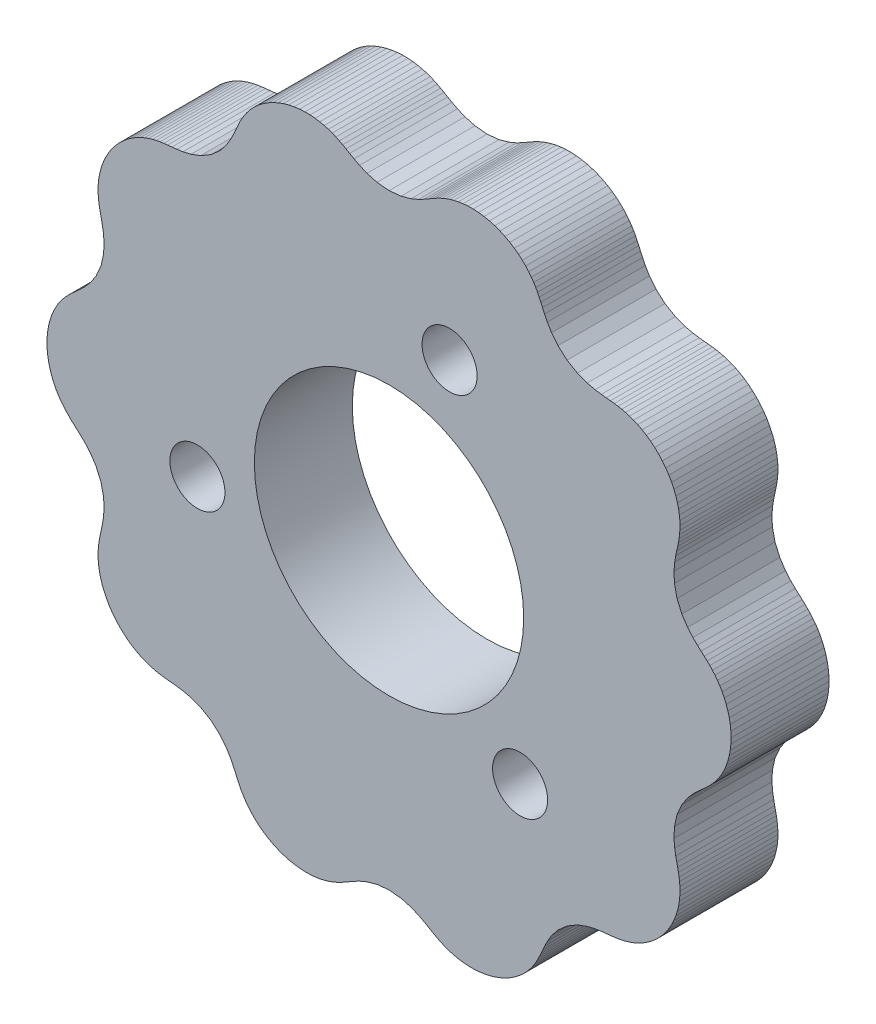
SolidWorks part; units mm, degrees
material "6061 Alloy"
ref_plane "Front Plane" through (0, 0, 0) normal (0, 0, 1) x (1, 0, 0)
ref_plane "Top Plane" through (0, 0, 0) normal (0, 1, 0) x (1, 0, 0)
ref_plane "Right Plane" through (0, 0, 0) normal (1, 0, 0) x (0, 0, -1)
sketch "Model" plane through (0, 0, 0) normal (0, 0, 1) x (1, 0, 0)
  line L0 (20.955, 0) -> (20.9416, 0.365) construction
  line L1 (20.9416, 0.365) -> (20.9019, 0.7253) construction
  line L2 (20.9019, 0.7253) -> (20.8371, 1.0767) construction
  line L3 (20.8371, 1.0767) -> (20.749, 1.4151) construction
  line L4 (20.749, 1.4151) -> (20.6403, 1.7368) construction
  line L5 (20.6403, 1.7368) -> (20.514, 2.0391) construction
  line L6 (20.514, 2.0391) -> (20.3735, 2.32) construction
  line L7 (20.3735, 2.32) -> (20.2221, 2.5783) construction
  line L8 (20.2221, 2.5783) -> (20.0631, 2.8139) construction
  line L9 (20.0631, 2.8139) -> (19.8992, 3.0281) construction
  line L10 (19.8992, 3.0281) -> (19.7321, 3.2232) construction
  line L11 (19.7321, 3.2232) -> (19.5618, 3.4033) construction
  line L12 (19.5618, 3.4033) -> (19.3864, 3.5744) construction
  line L13 (19.3864, 3.5744) -> (19.2007, 3.7451) construction
  line L14 (19.2007, 3.7451) -> (18.9953, 3.9287) construction
  line L15 (18.9953, 3.9287) -> (18.7567, 4.1455) construction
  line L16 (18.7567, 4.1455) -> (18.4694, 4.4274) construction
  line L17 (18.4694, 4.4274) -> (18.1274, 4.8212) construction
  line L18 (18.1274, 4.8212) -> (17.7602, 5.3749) construction
  line L19 (17.7602, 5.3749) -> (17.4515, 6.083) construction
  line L20 (17.4515, 6.083) -> (17.285, 6.8373) construction
  line L21 (17.285, 6.8373) -> (17.2567, 7.5011) construction
  line L22 (17.2567, 7.5011) -> (17.3019, 8.0207) construction
  line L23 (17.3019, 8.0207) -> (17.3686, 8.4177) construction
  line L24 (17.3686, 8.4177) -> (17.4342, 8.7332) construction
  line L25 (17.4342, 8.7332) -> (17.4925, 9.0025) construction
  line L26 (17.4925, 9.0025) -> (17.5424, 9.2498) construction
  line L27 (17.5424, 9.2498) -> (17.5837, 9.4913) construction
  line L28 (17.5837, 9.4913) -> (17.6156, 9.7371) construction
  line L29 (17.6156, 9.7371) -> (17.6361, 9.9932) construction
  line L30 (17.6361, 9.9932) -> (17.6428, 10.2628) construction
  line L31 (17.6428, 10.2628) -> (17.6329, 10.5469) construction
  line L32 (17.6329, 10.5469) -> (17.6036, 10.8448) construction
  line L33 (17.6036, 10.8448) -> (17.5522, 11.1546) construction
  line L34 (17.5522, 11.1546) -> (17.4767, 11.4734) construction
  line L35 (17.4767, 11.4734) -> (17.3755, 11.7977) construction
  line L36 (17.3755, 11.7977) -> (17.2479, 12.1231) construction
  line L37 (17.2479, 12.1231) -> (17.0938, 12.4455) construction
  line L38 (17.0938, 12.4455) -> (16.9141, 12.7604) construction
  line L39 (16.9141, 12.7604) -> (16.7104, 13.0635) construction
  line L40 (16.7104, 13.0635) -> (16.4851, 13.3509) construction
  line L41 (16.4851, 13.3509) -> (16.2411, 13.6191) construction
  line L42 (16.2411, 13.6191) -> (15.9821, 13.8653) construction
  line L43 (15.9821, 13.8653) -> (15.712, 14.0873) construction
  line L44 (15.712, 14.0873) -> (15.4349, 14.2837) construction
  line L45 (15.4349, 14.2837) -> (15.1551, 14.454) construction
  line L46 (15.1551, 14.454) -> (14.8763, 14.5986) construction
  line L47 (14.8763, 14.5986) -> (14.602, 14.7186) construction
  line L48 (14.602, 14.7186) -> (14.3349, 14.8158) construction
  line L49 (14.3349, 14.8158) -> (14.0764, 14.8927) construction
  line L50 (14.0764, 14.8927) -> (13.8265, 14.9523) construction
  line L51 (13.8265, 14.9523) -> (13.5829, 14.998) construction
  line L52 (13.5829, 14.998) -> (13.3405, 15.0333) construction
  line L53 (13.3405, 15.0333) -> (13.0898, 15.0622) construction
  line L54 (13.0898, 15.0622) -> (12.8157, 15.0901) construction
  line L55 (12.8157, 15.0901) -> (12.4953, 15.1252) construction
  line L56 (12.4953, 15.1252) -> (12.0972, 15.1844) construction
  line L57 (12.0972, 15.1844) -> (11.589, 15.302) construction
  line L58 (11.589, 15.302) -> (10.9665, 15.534) construction
  line L59 (10.9665, 15.534) -> (10.3006, 15.9255) construction
  line L60 (10.3006, 15.9255) -> (9.7225, 16.4379) construction
  line L61 (9.7225, 16.4379) -> (9.3094, 16.9582) construction
  line L62 (9.3094, 16.9582) -> (9.0405, 17.4052) construction
  line L63 (9.0405, 17.4052) -> (8.8612, 17.7655) construction
  line L64 (8.8612, 17.7655) -> (8.7288, 18.0594) construction
  line L65 (8.7288, 18.0594) -> (8.6176, 18.3115) construction
  line L66 (8.6176, 18.3115) -> (8.5126, 18.5409) construction
  line L67 (8.5126, 18.5409) -> (8.4041, 18.7606) construction
  line L68 (8.4041, 18.7606) -> (8.2854, 18.9781) construction
  line L69 (8.2854, 18.9781) -> (8.1515, 19.1974) construction
  line L70 (8.1515, 19.1974) -> (7.9985, 19.4194) construction
  line L71 (7.9985, 19.4194) -> (7.8235, 19.6434) construction
  line L72 (7.8235, 19.6434) -> (7.6246, 19.8672) construction
  line L73 (7.6246, 19.8672) -> (7.401, 20.0877) construction
  line L74 (7.401, 20.0877) -> (7.1525, 20.3012) construction
  line L75 (7.1525, 20.3012) -> (6.8801, 20.5041) construction
  line L76 (6.8801, 20.5041) -> (6.5855, 20.6924) construction
  line L77 (6.5855, 20.6924) -> (6.2713, 20.8626) construction
  line L78 (6.2713, 20.8626) -> (5.9409, 21.0117) construction
  line L79 (5.9409, 21.0117) -> (5.5979, 21.1372) construction
  line L80 (5.5979, 21.1372) -> (5.2467, 21.2373) construction
  line L81 (5.2467, 21.2373) -> (4.8917, 21.3109) construction
  line L82 (4.8917, 21.3109) -> (4.5374, 21.3578) construction
  line L83 (4.5374, 21.3578) -> (4.1885, 21.3786) construction
  line L84 (4.1885, 21.3786) -> (3.8489, 21.3747) construction
  line L85 (3.8489, 21.3747) -> (3.5223, 21.348) construction
  line L86 (3.5223, 21.348) -> (3.2118, 21.3011) construction
  line L87 (3.2118, 21.3011) -> (2.9193, 21.2369) construction
  line L88 (2.9193, 21.2369) -> (2.6461, 21.1585) construction
  line L89 (2.6461, 21.1585) -> (2.3918, 21.0688) construction
  line L90 (2.3918, 21.0688) -> (2.1545, 20.9702) construction
  line L91 (2.1545, 20.9702) -> (1.9307, 20.8639) construction
  line L92 (1.9307, 20.8639) -> (1.7138, 20.75) construction
  line L93 (1.7138, 20.75) -> (1.4939, 20.6261) construction
  line L94 (1.4939, 20.6261) -> (1.2559, 20.4875) construction
  line L95 (1.2559, 20.4875) -> (0.976, 20.3276) construction
  line L96 (0.976, 20.3276) -> (0.6191, 20.1415) construction
  line L97 (0.6191, 20.1415) -> (0.1389, 19.9379) construction
  line L98 (0.1389, 19.9379) -> (-0.5012, 19.7597) construction
  line L99 (-0.5012, 19.7597) -> (-1.27, 19.685) construction
  line L100 (-1.27, 19.685) -> (-2.0388, 19.7597) construction
  line L101 (-2.0388, 19.7597) -> (-2.6789, 19.9379) construction
  line L102 (-2.6789, 19.9379) -> (-3.1591, 20.1415) construction
  line L103 (-3.1591, 20.1415) -> (-3.516, 20.3276) construction
  line L104 (-3.516, 20.3276) -> (-3.7959, 20.4875) construction
  line L105 (-3.7959, 20.4875) -> (-4.0339, 20.6261) construction
  line L106 (-4.0339, 20.6261) -> (-4.2538, 20.75) construction
  line L107 (-4.2538, 20.75) -> (-4.4707, 20.8639) construction
  line L108 (-4.4707, 20.8639) -> (-4.6945, 20.9702) construction
  line L109 (-4.6945, 20.9702) -> (-4.9318, 21.0688) construction
  line L110 (-4.9318, 21.0688) -> (-5.1861, 21.1585) construction
  line L111 (-5.1861, 21.1585) -> (-5.4593, 21.2369) construction
  line L112 (-5.4593, 21.2369) -> (-5.7518, 21.3011) construction
  line L113 (-5.7518, 21.3011) -> (-6.0623, 21.348) construction
  line L114 (-6.0623, 21.348) -> (-6.3889, 21.3747) construction
  line L115 (-6.3889, 21.3747) -> (-6.7285, 21.3786) construction
  line L116 (-6.7285, 21.3786) -> (-7.0774, 21.3578) construction
  line L117 (-7.0774, 21.3578) -> (-7.4317, 21.3109) construction
  line L118 (-7.4317, 21.3109) -> (-7.7867, 21.2373) construction
  line L119 (-7.7867, 21.2373) -> (-8.1379, 21.1372) construction
  line L120 (-8.1379, 21.1372) -> (-8.4809, 21.0117) construction
  line L121 (-8.4809, 21.0117) -> (-8.8113, 20.8626) construction
  line L122 (-8.8113, 20.8626) -> (-9.1255, 20.6924) construction
  line L123 (-9.1255, 20.6924) -> (-9.4201, 20.5041) construction
  line L124 (-9.4201, 20.5041) -> (-9.6925, 20.3012) construction
  line L125 (-9.6925, 20.3012) -> (-9.941, 20.0877) construction
  line L126 (-9.941, 20.0877) -> (-10.1646, 19.8672) construction
  line L127 (-10.1646, 19.8672) -> (-10.3635, 19.6434) construction
  line L128 (-10.3635, 19.6434) -> (-10.5385, 19.4194) construction
  line L129 (-10.5385, 19.4194) -> (-10.6915, 19.1974) construction
  line L130 (-10.6915, 19.1974) -> (-10.8254, 18.9781) construction
  line L131 (-10.8254, 18.9781) -> (-10.9441, 18.7606) construction
  line L132 (-10.9441, 18.7606) -> (-11.0526, 18.5409) construction
  line L133 (-11.0526, 18.5409) -> (-11.1576, 18.3115) construction
  line L134 (-11.1576, 18.3115) -> (-11.2688, 18.0594) construction
  line L135 (-11.2688, 18.0594) -> (-11.4012, 17.7655) construction
  line L136 (-11.4012, 17.7655) -> (-11.5805, 17.4052) construction
  line L137 (-11.5805, 17.4052) -> (-11.8494, 16.9582) construction
  line L138 (-11.8494, 16.9582) -> (-12.2625, 16.4379) construction
  line L139 (-12.2625, 16.4379) -> (-12.8406, 15.9255) construction
  line L140 (-12.8406, 15.9255) -> (-13.5065, 15.534) construction
  line L141 (-13.5065, 15.534) -> (-14.129, 15.302) construction
  line L142 (-14.129, 15.302) -> (-14.6372, 15.1844) construction
  line L143 (-14.6372, 15.1844) -> (-15.0353, 15.1252) construction
  line L144 (-15.0353, 15.1252) -> (-15.3557, 15.0901) construction
  line L145 (-15.3557, 15.0901) -> (-15.6298, 15.0622) construction
  line L146 (-15.6298, 15.0622) -> (-15.8805, 15.0333) construction
  line L147 (-15.8805, 15.0333) -> (-16.1229, 14.998) construction
  line L148 (-16.1229, 14.998) -> (-16.3665, 14.9523) construction
  line L149 (-16.3665, 14.9523) -> (-16.6164, 14.8927) construction
  line L150 (-16.6164, 14.8927) -> (-16.8749, 14.8158) construction
  line L151 (-16.8749, 14.8158) -> (-17.142, 14.7186) construction
  line L152 (-17.142, 14.7186) -> (-17.4163, 14.5986) construction
  line L153 (-17.4163, 14.5986) -> (-17.6951, 14.454) construction
  line L154 (-17.6951, 14.454) -> (-17.9749, 14.2837) construction
  line L155 (-17.9749, 14.2837) -> (-18.252, 14.0873) construction
  line L156 (-18.252, 14.0873) -> (-18.5221, 13.8653) construction
  line L157 (-18.5221, 13.8653) -> (-18.7811, 13.6191) construction
  line L158 (-18.7811, 13.6191) -> (-19.0251, 13.3509) construction
  line L159 (-19.0251, 13.3509) -> (-19.2504, 13.0635) construction
  line L160 (-19.2504, 13.0635) -> (-19.4541, 12.7604) construction
  line L161 (-19.4541, 12.7604) -> (-19.6338, 12.4455) construction
  line L162 (-19.6338, 12.4455) -> (-19.7879, 12.1231) construction
  line L163 (-19.7879, 12.1231) -> (-19.9155, 11.7977) construction
  line L164 (-19.9155, 11.7977) -> (-20.0167, 11.4734) construction
  line L165 (-20.0167, 11.4734) -> (-20.0922, 11.1546) construction
  line L166 (-20.0922, 11.1546) -> (-20.1436, 10.8448) construction
  line L167 (-20.1436, 10.8448) -> (-20.1729, 10.5469) construction
  line L168 (-20.1729, 10.5469) -> (-20.1828, 10.2628) construction
  line L169 (-20.1828, 10.2628) -> (-20.1761, 9.9932) construction
  line L170 (-20.1761, 9.9932) -> (-20.1556, 9.7371) construction
  line L171 (-20.1556, 9.7371) -> (-20.1237, 9.4913) construction
  line L172 (-20.1237, 9.4913) -> (-20.0824, 9.2498) construction
  line L173 (-20.0824, 9.2498) -> (-20.0325, 9.0025) construction
  line L174 (-20.0325, 9.0025) -> (-19.9742, 8.7332) construction
  line L175 (-19.9742, 8.7332) -> (-19.9086, 8.4177) construction
  line L176 (-19.9086, 8.4177) -> (-19.8419, 8.0207) construction
  line L177 (-19.8419, 8.0207) -> (-19.7967, 7.5011) construction
  line L178 (-19.7967, 7.5011) -> (-19.825, 6.8373) construction
  line L179 (-19.825, 6.8373) -> (-19.9915, 6.083) construction
  line L180 (-19.9915, 6.083) -> (-20.3002, 5.3749) construction
  line L181 (-20.3002, 5.3749) -> (-20.6674, 4.8212) construction
  line L182 (-20.6674, 4.8212) -> (-21.0094, 4.4274) construction
  line L183 (-21.0094, 4.4274) -> (-21.2967, 4.1455) construction
  line L184 (-21.2967, 4.1455) -> (-21.5353, 3.9287) construction
  line L185 (-21.5353, 3.9287) -> (-21.7407, 3.7451) construction
  line L186 (-21.7407, 3.7451) -> (-21.9264, 3.5744) construction
  line L187 (-21.9264, 3.5744) -> (-22.1018, 3.4033) construction
  line L188 (-22.1018, 3.4033) -> (-22.2721, 3.2232) construction
  line L189 (-22.2721, 3.2232) -> (-22.4392, 3.0281) construction
  line L190 (-22.4392, 3.0281) -> (-22.6031, 2.8139) construction
  line L191 (-22.6031, 2.8139) -> (-22.7621, 2.5783) construction
  line L192 (-22.7621, 2.5783) -> (-22.9135, 2.32) construction
  line L193 (-22.9135, 2.32) -> (-23.054, 2.0391) construction
  line L194 (-23.054, 2.0391) -> (-23.1803, 1.7368) construction
  line L195 (-23.1803, 1.7368) -> (-23.289, 1.4151) construction
  line L196 (-23.289, 1.4151) -> (-23.3771, 1.0767) construction
  line L197 (-23.3771, 1.0767) -> (-23.4419, 0.7253) construction
  line L198 (-23.4419, 0.7253) -> (-23.4816, 0.365) construction
  line L199 (-23.4816, 0.365) -> (-23.495, 0) construction
  line L200 (-23.495, 0) -> (-23.4816, -0.365) construction
  line L201 (-23.4816, -0.365) -> (-23.4419, -0.7253) construction
  line L202 (-23.4419, -0.7253) -> (-23.3771, -1.0767) construction
  line L203 (-23.3771, -1.0767) -> (-23.289, -1.4151) construction
  line L204 (-23.289, -1.4151) -> (-23.1803, -1.7368) construction
  line L205 (-23.1803, -1.7368) -> (-23.054, -2.0391) construction
  line L206 (-23.054, -2.0391) -> (-22.9135, -2.32) construction
  line L207 (-22.9135, -2.32) -> (-22.7621, -2.5783) construction
  line L208 (-22.7621, -2.5783) -> (-22.6031, -2.8139) construction
  line L209 (-22.6031, -2.8139) -> (-22.4392, -3.0281) construction
  line L210 (-22.4392, -3.0281) -> (-22.2721, -3.2232) construction
  line L211 (-22.2721, -3.2232) -> (-22.1018, -3.4033) construction
  line L212 (-22.1018, -3.4033) -> (-21.9264, -3.5744) construction
  line L213 (-21.9264, -3.5744) -> (-21.7407, -3.7451) construction
  line L214 (-21.7407, -3.7451) -> (-21.5353, -3.9287) construction
  line L215 (-21.5353, -3.9287) -> (-21.2967, -4.1455) construction
  line L216 (-21.2967, -4.1455) -> (-21.0094, -4.4274) construction
  line L217 (-21.0094, -4.4274) -> (-20.6674, -4.8212) construction
  line L218 (-20.6674, -4.8212) -> (-20.3002, -5.3749) construction
  line L219 (-20.3002, -5.3749) -> (-19.9915, -6.083) construction
  line L220 (-19.9915, -6.083) -> (-19.825, -6.8373) construction
  line L221 (-19.825, -6.8373) -> (-19.7967, -7.5011) construction
  line L222 (-19.7967, -7.5011) -> (-19.8419, -8.0207) construction
  line L223 (-19.8419, -8.0207) -> (-19.9086, -8.4177) construction
  line L224 (-19.9086, -8.4177) -> (-19.9742, -8.7332) construction
  line L225 (-19.9742, -8.7332) -> (-20.0325, -9.0025) construction
  line L226 (-20.0325, -9.0025) -> (-20.0824, -9.2498) construction
  line L227 (-20.0824, -9.2498) -> (-20.1237, -9.4913) construction
  line L228 (-20.1237, -9.4913) -> (-20.1556, -9.7371) construction
  line L229 (-20.1556, -9.7371) -> (-20.1761, -9.9932) construction
  line L230 (-20.1761, -9.9932) -> (-20.1828, -10.2628) construction
  line L231 (-20.1828, -10.2628) -> (-20.1729, -10.5469) construction
  line L232 (-20.1729, -10.5469) -> (-20.1436, -10.8448) construction
  line L233 (-20.1436, -10.8448) -> (-20.0922, -11.1546) construction
  line L234 (-20.0922, -11.1546) -> (-20.0167, -11.4734) construction
  line L235 (-20.0167, -11.4734) -> (-19.9155, -11.7977) construction
  line L236 (-19.9155, -11.7977) -> (-19.7879, -12.1231) construction
  line L237 (-19.7879, -12.1231) -> (-19.6338, -12.4455) construction
  line L238 (-19.6338, -12.4455) -> (-19.4541, -12.7604) construction
  line L239 (-19.4541, -12.7604) -> (-19.2504, -13.0635) construction
  line L240 (-19.2504, -13.0635) -> (-19.0251, -13.3509) construction
  line L241 (-19.0251, -13.3509) -> (-18.7811, -13.6191) construction
  line L242 (-18.7811, -13.6191) -> (-18.5221, -13.8653) construction
  line L243 (-18.5221, -13.8653) -> (-18.252, -14.0873) construction
  line L244 (-18.252, -14.0873) -> (-17.9749, -14.2837) construction
  line L245 (-17.9749, -14.2837) -> (-17.6951, -14.454) construction
  line L246 (-17.6951, -14.454) -> (-17.4163, -14.5986) construction
  line L247 (-17.4163, -14.5986) -> (-17.142, -14.7186) construction
  line L248 (-17.142, -14.7186) -> (-16.8749, -14.8158) construction
  line L249 (-16.8749, -14.8158) -> (-16.6164, -14.8927) construction
  line L250 (-16.6164, -14.8927) -> (-16.3665, -14.9523) construction
  line L251 (-16.3665, -14.9523) -> (-16.1229, -14.998) construction
  line L252 (-16.1229, -14.998) -> (-15.8805, -15.0333) construction
  line L253 (-15.8805, -15.0333) -> (-15.6298, -15.0622) construction
  line L254 (-15.6298, -15.0622) -> (-15.3557, -15.0901) construction
  line L255 (-15.3557, -15.0901) -> (-15.0353, -15.1252) construction
  line L256 (-15.0353, -15.1252) -> (-14.6372, -15.1844) construction
  line L257 (-14.6372, -15.1844) -> (-14.129, -15.302) construction
  line L258 (-14.129, -15.302) -> (-13.5065, -15.534) construction
  line L259 (-13.5065, -15.534) -> (-12.8406, -15.9255) construction
  line L260 (-12.8406, -15.9255) -> (-12.2625, -16.4379) construction
  line L261 (-12.2625, -16.4379) -> (-11.8494, -16.9582) construction
  line L262 (-11.8494, -16.9582) -> (-11.5805, -17.4052) construction
  line L263 (-11.5805, -17.4052) -> (-11.4012, -17.7655) construction
  line L264 (-11.4012, -17.7655) -> (-11.2688, -18.0594) construction
  line L265 (-11.2688, -18.0594) -> (-11.1576, -18.3115) construction
  line L266 (-11.1576, -18.3115) -> (-11.0526, -18.5409) construction
  line L267 (-11.0526, -18.5409) -> (-10.9441, -18.7606) construction
  line L268 (-10.9441, -18.7606) -> (-10.8254, -18.9781) construction
  line L269 (-10.8254, -18.9781) -> (-10.6915, -19.1974) construction
  line L270 (-10.6915, -19.1974) -> (-10.5385, -19.4194) construction
  line L271 (-10.5385, -19.4194) -> (-10.3635, -19.6434) construction
  line L272 (-10.3635, -19.6434) -> (-10.1646, -19.8672) construction
  line L273 (-10.1646, -19.8672) -> (-9.941, -20.0877) construction
  line L274 (-9.941, -20.0877) -> (-9.6925, -20.3012) construction
  line L275 (-9.6925, -20.3012) -> (-9.4201, -20.5041) construction
  line L276 (-9.4201, -20.5041) -> (-9.1255, -20.6924) construction
  line L277 (-9.1255, -20.6924) -> (-8.8113, -20.8626) construction
  line L278 (-8.8113, -20.8626) -> (-8.4809, -21.0117) construction
  line L279 (-8.4809, -21.0117) -> (-8.1379, -21.1372) construction
  line L280 (-8.1379, -21.1372) -> (-7.7867, -21.2373) construction
  line L281 (-7.7867, -21.2373) -> (-7.4317, -21.3109) construction
  line L282 (-7.4317, -21.3109) -> (-7.0774, -21.3578) construction
  line L283 (-7.0774, -21.3578) -> (-6.7285, -21.3786) construction
  line L284 (-6.7285, -21.3786) -> (-6.3889, -21.3747) construction
  line L285 (-6.3889, -21.3747) -> (-6.0623, -21.348) construction
  line L286 (-6.0623, -21.348) -> (-5.7518, -21.3011) construction
  line L287 (-5.7518, -21.3011) -> (-5.4593, -21.2369) construction
  line L288 (-5.4593, -21.2369) -> (-5.1861, -21.1585) construction
  line L289 (-5.1861, -21.1585) -> (-4.9318, -21.0688) construction
  line L290 (-4.9318, -21.0688) -> (-4.6945, -20.9702) construction
  line L291 (-4.6945, -20.9702) -> (-4.4707, -20.8639) construction
  line L292 (-4.4707, -20.8639) -> (-4.2538, -20.75) construction
  line L293 (-4.2538, -20.75) -> (-4.0339, -20.6261) construction
  line L294 (-4.0339, -20.6261) -> (-3.7959, -20.4875) construction
  line L295 (-3.7959, -20.4875) -> (-3.516, -20.3276) construction
  line L296 (-3.516, -20.3276) -> (-3.1591, -20.1415) construction
  line L297 (-3.1591, -20.1415) -> (-2.6789, -19.9379) construction
  line L298 (-2.6789, -19.9379) -> (-2.0388, -19.7597) construction
  line L299 (-2.0388, -19.7597) -> (-1.27, -19.685) construction
  line L300 (-1.27, -19.685) -> (-0.5012, -19.7597) construction
  line L301 (-0.5012, -19.7597) -> (0.1389, -19.9379) construction
  line L302 (0.1389, -19.9379) -> (0.6191, -20.1415) construction
  line L303 (0.6191, -20.1415) -> (0.976, -20.3276) construction
  line L304 (0.976, -20.3276) -> (1.2559, -20.4875) construction
  line L305 (1.2559, -20.4875) -> (1.4939, -20.6261) construction
  line L306 (1.4939, -20.6261) -> (1.7138, -20.75) construction
  line L307 (1.7138, -20.75) -> (1.9307, -20.8639) construction
  line L308 (1.9307, -20.8639) -> (2.1545, -20.9702) construction
  line L309 (2.1545, -20.9702) -> (2.3918, -21.0688) construction
  line L310 (2.3918, -21.0688) -> (2.6461, -21.1585) construction
  line L311 (2.6461, -21.1585) -> (2.9193, -21.2369) construction
  line L312 (2.9193, -21.2369) -> (3.2118, -21.3011) construction
  line L313 (3.2118, -21.3011) -> (3.5223, -21.348) construction
  line L314 (3.5223, -21.348) -> (3.8489, -21.3747) construction
  line L315 (3.8489, -21.3747) -> (4.1885, -21.3786) construction
  line L316 (4.1885, -21.3786) -> (4.5374, -21.3578) construction
  line L317 (4.5374, -21.3578) -> (4.8917, -21.3109) construction
  line L318 (4.8917, -21.3109) -> (5.2467, -21.2373) construction
  line L319 (5.2467, -21.2373) -> (5.5979, -21.1372) construction
  line L320 (5.5979, -21.1372) -> (5.9409, -21.0117) construction
  line L321 (5.9409, -21.0117) -> (6.2713, -20.8626) construction
  line L322 (6.2713, -20.8626) -> (6.5855, -20.6924) construction
  line L323 (6.5855, -20.6924) -> (6.8801, -20.5041) construction
  line L324 (6.8801, -20.5041) -> (7.1525, -20.3012) construction
  line L325 (7.1525, -20.3012) -> (7.401, -20.0877) construction
  line L326 (7.401, -20.0877) -> (7.6246, -19.8672) construction
  line L327 (7.6246, -19.8672) -> (7.8235, -19.6434) construction
  line L328 (7.8235, -19.6434) -> (7.9985, -19.4194) construction
  line L329 (7.9985, -19.4194) -> (8.1515, -19.1974) construction
  line L330 (8.1515, -19.1974) -> (8.2854, -18.9781) construction
  line L331 (8.2854, -18.9781) -> (8.4041, -18.7606) construction
  line L332 (8.4041, -18.7606) -> (8.5126, -18.5409) construction
  line L333 (8.5126, -18.5409) -> (8.6176, -18.3115) construction
  line L334 (8.6176, -18.3115) -> (8.7288, -18.0594) construction
  line L335 (8.7288, -18.0594) -> (8.8612, -17.7655) construction
  line L336 (8.8612, -17.7655) -> (9.0405, -17.4052) construction
  line L337 (9.0405, -17.4052) -> (9.3094, -16.9582) construction
  line L338 (9.3094, -16.9582) -> (9.7225, -16.4379) construction
  line L339 (9.7225, -16.4379) -> (10.3006, -15.9255) construction
  line L340 (10.3006, -15.9255) -> (10.9665, -15.534) construction
  line L341 (10.9665, -15.534) -> (11.589, -15.302) construction
  line L342 (11.589, -15.302) -> (12.0972, -15.1844) construction
  line L343 (12.0972, -15.1844) -> (12.4953, -15.1252) construction
  line L344 (12.4953, -15.1252) -> (12.8157, -15.0901) construction
  line L345 (12.8157, -15.0901) -> (13.0898, -15.0622) construction
  line L346 (13.0898, -15.0622) -> (13.3405, -15.0333) construction
  line L347 (13.3405, -15.0333) -> (13.5829, -14.998) construction
  line L348 (13.5829, -14.998) -> (13.8265, -14.9523) construction
  line L349 (13.8265, -14.9523) -> (14.0764, -14.8927) construction
  line L350 (14.0764, -14.8927) -> (14.3349, -14.8158) construction
  line L351 (14.3349, -14.8158) -> (14.602, -14.7186) construction
  line L352 (14.602, -14.7186) -> (14.8763, -14.5986) construction
  line L353 (14.8763, -14.5986) -> (15.1551, -14.454) construction
  line L354 (15.1551, -14.454) -> (15.4349, -14.2837) construction
  line L355 (15.4349, -14.2837) -> (15.712, -14.0873) construction
  line L356 (15.712, -14.0873) -> (15.9821, -13.8653) construction
  line L357 (15.9821, -13.8653) -> (16.2411, -13.6191) construction
  line L358 (16.2411, -13.6191) -> (16.4851, -13.3509) construction
  line L359 (16.4851, -13.3509) -> (16.7104, -13.0635) construction
  line L360 (16.7104, -13.0635) -> (16.9141, -12.7604) construction
  line L361 (16.9141, -12.7604) -> (17.0938, -12.4455) construction
  line L362 (17.0938, -12.4455) -> (17.2479, -12.1231) construction
  line L363 (17.2479, -12.1231) -> (17.3755, -11.7977) construction
  line L364 (17.3755, -11.7977) -> (17.4767, -11.4734) construction
  line L365 (17.4767, -11.4734) -> (17.5522, -11.1546) construction
  line L366 (17.5522, -11.1546) -> (17.6036, -10.8448) construction
  line L367 (17.6036, -10.8448) -> (17.6329, -10.5469) construction
  line L368 (17.6329, -10.5469) -> (17.6428, -10.2628) construction
  line L369 (17.6428, -10.2628) -> (17.6361, -9.9932) construction
  line L370 (17.6361, -9.9932) -> (17.6156, -9.7371) construction
  line L371 (17.6156, -9.7371) -> (17.5837, -9.4913) construction
  line L372 (17.5837, -9.4913) -> (17.5424, -9.2498) construction
  line L373 (17.5424, -9.2498) -> (17.4925, -9.0025) construction
  line L374 (17.4925, -9.0025) -> (17.4342, -8.7332) construction
  line L375 (17.4342, -8.7332) -> (17.3686, -8.4177) construction
  line L376 (17.3686, -8.4177) -> (17.3019, -8.0207) construction
  line L377 (17.3019, -8.0207) -> (17.2567, -7.5011) construction
  line L378 (17.2567, -7.5011) -> (17.285, -6.8373) construction
  line L379 (17.285, -6.8373) -> (17.4515, -6.083) construction
  line L380 (17.4515, -6.083) -> (17.7602, -5.3749) construction
  line L381 (17.7602, -5.3749) -> (18.1274, -4.8212) construction
  line L382 (18.1274, -4.8212) -> (18.4694, -4.4274) construction
  line L383 (18.4694, -4.4274) -> (18.7567, -4.1455) construction
  line L384 (18.7567, -4.1455) -> (18.9953, -3.9287) construction
  line L385 (18.9953, -3.9287) -> (19.2007, -3.7451) construction
  line L386 (19.2007, -3.7451) -> (19.3864, -3.5744) construction
  line L387 (19.3864, -3.5744) -> (19.5618, -3.4033) construction
  line L388 (19.5618, -3.4033) -> (19.7321, -3.2232) construction
  line L389 (19.7321, -3.2232) -> (19.8992, -3.0281) construction
  line L390 (19.8992, -3.0281) -> (20.0631, -2.8139) construction
  line L391 (20.0631, -2.8139) -> (20.2221, -2.5783) construction
  line L392 (20.2221, -2.5783) -> (20.3735, -2.32) construction
  line L393 (20.3735, -2.32) -> (20.514, -2.0391) construction
  line L394 (20.514, -2.0391) -> (20.6403, -1.7368) construction
  line L395 (20.6403, -1.7368) -> (20.749, -1.4151) construction
  line L396 (20.749, -1.4151) -> (20.8371, -1.0767) construction
  line L397 (20.8371, -1.0767) -> (20.9019, -0.7253) construction
  line L398 (20.9019, -0.7253) -> (20.9416, -0.365) construction
  line L399 (20.9416, -0.365) -> (20.955, 0) construction
  line L400 (20.9042, 0) -> (20.8909, 0.3612)
  line L401 (20.8909, 0.3612) -> (20.8516, 0.7179)
  line L402 (20.8516, 0.7179) -> (20.7875, 1.0657)
  line L403 (20.7875, 1.0657) -> (20.7003, 1.4005)
  line L404 (20.7003, 1.4005) -> (20.5928, 1.7189)
  line L405 (20.5928, 1.7189) -> (20.4678, 2.018)
  line L406 (20.4678, 2.018) -> (20.3288, 2.2958)
  line L407 (20.3288, 2.2958) -> (20.1791, 2.5512)
  line L408 (20.1791, 2.5512) -> (20.0218, 2.7843)
  line L409 (20.0218, 2.7843) -> (19.8597, 2.9961)
  line L410 (19.8597, 2.9961) -> (19.6943, 3.1892)
  line L411 (19.6943, 3.1892) -> (19.5256, 3.3677)
  line L412 (19.5256, 3.3677) -> (19.3515, 3.5375)
  line L413 (19.3515, 3.5375) -> (19.1666, 3.7075)
  line L414 (19.1666, 3.7075) -> (18.9613, 3.891)
  line L415 (18.9613, 3.891) -> (18.7218, 4.1085)
  line L416 (18.7218, 4.1085) -> (18.4324, 4.3925)
  line L417 (18.4324, 4.3925) -> (18.0869, 4.7904)
  line L418 (18.0869, 4.7904) -> (17.7154, 5.3505)
  line L419 (17.7154, 5.3505) -> (17.403, 6.0672)
  line L420 (17.403, 6.0672) -> (17.2345, 6.8307)
  line L421 (17.2345, 6.8307) -> (17.2058, 7.5022)
  line L422 (17.2058, 7.5022) -> (17.2515, 8.0271)
  line L423 (17.2515, 8.0271) -> (17.3187, 8.427)
  line L424 (17.3187, 8.427) -> (17.3845, 8.7438)
  line L425 (17.3845, 8.7438) -> (17.4427, 9.0129)
  line L426 (17.4427, 9.0129) -> (17.4924, 9.2591)
  line L427 (17.4924, 9.2591) -> (17.5335, 9.4989)
  line L428 (17.5335, 9.4989) -> (17.565, 9.7424)
  line L429 (17.565, 9.7424) -> (17.5854, 9.9958)
  line L430 (17.5854, 9.9958) -> (17.592, 10.2625)
  line L431 (17.592, 10.2625) -> (17.5822, 10.5435)
  line L432 (17.5822, 10.5435) -> (17.5532, 10.8381)
  line L433 (17.5532, 10.8381) -> (17.5024, 11.1446)
  line L434 (17.5024, 11.1446) -> (17.4277, 11.46)
  line L435 (17.4277, 11.46) -> (17.3276, 11.7808)
  line L436 (17.3276, 11.7808) -> (17.2013, 12.1029)
  line L437 (17.2013, 12.1029) -> (17.0488, 12.4219)
  line L438 (17.0488, 12.4219) -> (16.8709, 12.7336)
  line L439 (16.8709, 12.7336) -> (16.6693, 13.0336)
  line L440 (16.6693, 13.0336) -> (16.4462, 13.3181)
  line L441 (16.4462, 13.3181) -> (16.2048, 13.5836)
  line L442 (16.2048, 13.5836) -> (15.9485, 13.8272)
  line L443 (15.9485, 13.8272) -> (15.6812, 14.0469)
  line L444 (15.6812, 14.0469) -> (15.407, 14.2412)
  line L445 (15.407, 14.2412) -> (15.1301, 14.4097)
  line L446 (15.1301, 14.4097) -> (14.8544, 14.5527)
  line L447 (14.8544, 14.5527) -> (14.5831, 14.6714)
  line L448 (14.5831, 14.6714) -> (14.3189, 14.7675)
  line L449 (14.3189, 14.7675) -> (14.0632, 14.8436)
  line L450 (14.0632, 14.8436) -> (13.8159, 14.9026)
  line L451 (13.8159, 14.9026) -> (13.5746, 14.9479)
  line L452 (13.5746, 14.9479) -> (13.3339, 14.9829)
  line L453 (13.3339, 14.9829) -> (13.0843, 15.0117)
  line L454 (13.0843, 15.0117) -> (12.8104, 15.0395)
  line L455 (12.8104, 15.0395) -> (12.4888, 15.0748)
  line L456 (12.4888, 15.0748) -> (12.0877, 15.1344)
  line L457 (12.0877, 15.1344) -> (11.5743, 15.2533)
  line L458 (11.5743, 15.2533) -> (10.9446, 15.488)
  line L459 (10.9446, 15.488) -> (10.2706, 15.8842)
  line L460 (10.2706, 15.8842) -> (9.6855, 16.4028)
  line L461 (9.6855, 16.4028) -> (9.2676, 16.9292)
  line L462 (9.2676, 16.9292) -> (8.9959, 17.3807)
  line L463 (8.9959, 17.3807) -> (8.8152, 17.7438)
  line L464 (8.8152, 17.7438) -> (8.6824, 18.0387)
  line L465 (8.6824, 18.0387) -> (8.5713, 18.2906)
  line L466 (8.5713, 18.2906) -> (8.4667, 18.5191)
  line L467 (8.4667, 18.5191) -> (8.359, 18.7372)
  line L468 (8.359, 18.7372) -> (8.2414, 18.9527)
  line L469 (8.2414, 18.9527) -> (8.1089, 19.1697)
  line L470 (8.1089, 19.1697) -> (7.9575, 19.3894)
  line L471 (7.9575, 19.3894) -> (7.7845, 19.6109)
  line L472 (7.7845, 19.6109) -> (7.5878, 19.8322)
  line L473 (7.5878, 19.8322) -> (7.3665, 20.0503)
  line L474 (7.3665, 20.0503) -> (7.1207, 20.2616)
  line L475 (7.1207, 20.2616) -> (6.8512, 20.4622)
  line L476 (6.8512, 20.4622) -> (6.5597, 20.6486)
  line L477 (6.5597, 20.6486) -> (6.2488, 20.8171)
  line L478 (6.2488, 20.8171) -> (5.9217, 20.9647)
  line L479 (5.9217, 20.9647) -> (5.5822, 21.0889)
  line L480 (5.5822, 21.0889) -> (5.2345, 21.1879)
  line L481 (5.2345, 21.1879) -> (4.8832, 21.2608)
  line L482 (4.8832, 21.2608) -> (4.5326, 21.3072)
  line L483 (4.5326, 21.3072) -> (4.1872, 21.3278)
  line L484 (4.1872, 21.3278) -> (3.8512, 21.3239)
  line L485 (3.8512, 21.3239) -> (3.5282, 21.2975)
  line L486 (3.5282, 21.2975) -> (3.221, 21.2511)
  line L487 (3.221, 21.2511) -> (2.9318, 21.1876)
  line L488 (2.9318, 21.1876) -> (2.6616, 21.1101)
  line L489 (2.6616, 21.1101) -> (2.41, 21.0214)
  line L490 (2.41, 21.0214) -> (2.1752, 20.9237)
  line L491 (2.1752, 20.9237) -> (1.9534, 20.8185)
  line L492 (1.9534, 20.8185) -> (1.7381, 20.7054)
  line L493 (1.7381, 20.7054) -> (1.5192, 20.582)
  line L494 (1.5192, 20.582) -> (1.2813, 20.4435)
  line L495 (1.2813, 20.4435) -> (1.0004, 20.283)
  line L496 (1.0004, 20.283) -> (0.6408, 20.0955)
  line L497 (0.6408, 20.0955) -> (0.1557, 19.8899)
  line L498 (0.1557, 19.8899) -> (-0.4918, 19.7096)
  line L499 (-0.4918, 19.7096) -> (-1.27, 19.634)
  line L500 (-1.27, 19.634) -> (-2.0482, 19.7096)
  line L501 (-2.0482, 19.7096) -> (-2.6957, 19.8899)
  line L502 (-2.6957, 19.8899) -> (-3.1808, 20.0955)
  line L503 (-3.1808, 20.0955) -> (-3.5404, 20.283)
  line L504 (-3.5404, 20.283) -> (-3.8213, 20.4435)
  line L505 (-3.8213, 20.4435) -> (-4.0592, 20.582)
  line L506 (-4.0592, 20.582) -> (-4.2781, 20.7054)
  line L507 (-4.2781, 20.7054) -> (-4.4934, 20.8185)
  line L508 (-4.4934, 20.8185) -> (-4.7152, 20.9237)
  line L509 (-4.7152, 20.9237) -> (-4.95, 21.0214)
  line L510 (-4.95, 21.0214) -> (-5.2016, 21.1101)
  line L511 (-5.2016, 21.1101) -> (-5.4718, 21.1876)
  line L512 (-5.4718, 21.1876) -> (-5.761, 21.2511)
  line L513 (-5.761, 21.2511) -> (-6.0682, 21.2975)
  line L514 (-6.0682, 21.2975) -> (-6.3912, 21.3239)
  line L515 (-6.3912, 21.3239) -> (-6.7272, 21.3278)
  line L516 (-6.7272, 21.3278) -> (-7.0726, 21.3072)
  line L517 (-7.0726, 21.3072) -> (-7.4232, 21.2608)
  line L518 (-7.4232, 21.2608) -> (-7.7745, 21.1879)
  line L519 (-7.7745, 21.1879) -> (-8.1222, 21.0889)
  line L520 (-8.1222, 21.0889) -> (-8.4617, 20.9647)
  line L521 (-8.4617, 20.9647) -> (-8.7888, 20.8171)
  line L522 (-8.7888, 20.8171) -> (-9.0997, 20.6486)
  line L523 (-9.0997, 20.6486) -> (-9.3912, 20.4622)
  line L524 (-9.3912, 20.4622) -> (-9.6607, 20.2616)
  line L525 (-9.6607, 20.2616) -> (-9.9065, 20.0503)
  line L526 (-9.9065, 20.0503) -> (-10.1278, 19.8322)
  line L527 (-10.1278, 19.8322) -> (-10.3245, 19.6109)
  line L528 (-10.3245, 19.6109) -> (-10.4975, 19.3894)
  line L529 (-10.4975, 19.3894) -> (-10.6489, 19.1697)
  line L530 (-10.6489, 19.1697) -> (-10.7814, 18.9527)
  line L531 (-10.7814, 18.9527) -> (-10.899, 18.7372)
  line L532 (-10.899, 18.7372) -> (-11.0067, 18.5191)
  line L533 (-11.0067, 18.5191) -> (-11.1113, 18.2906)
  line L534 (-11.1113, 18.2906) -> (-11.2224, 18.0387)
  line L535 (-11.2224, 18.0387) -> (-11.3552, 17.7438)
  line L536 (-11.3552, 17.7438) -> (-11.5359, 17.3807)
  line L537 (-11.5359, 17.3807) -> (-11.8076, 16.9292)
  line L538 (-11.8076, 16.9292) -> (-12.2255, 16.4028)
  line L539 (-12.2255, 16.4028) -> (-12.8106, 15.8842)
  line L540 (-12.8106, 15.8842) -> (-13.4846, 15.488)
  line L541 (-13.4846, 15.488) -> (-14.1143, 15.2533)
  line L542 (-14.1143, 15.2533) -> (-14.6277, 15.1344)
  line L543 (-14.6277, 15.1344) -> (-15.0288, 15.0748)
  line L544 (-15.0288, 15.0748) -> (-15.3504, 15.0395)
  line L545 (-15.3504, 15.0395) -> (-15.6243, 15.0117)
  line L546 (-15.6243, 15.0117) -> (-15.8739, 14.9829)
  line L547 (-15.8739, 14.9829) -> (-16.1146, 14.9479)
  line L548 (-16.1146, 14.9479) -> (-16.3559, 14.9026)
  line L549 (-16.3559, 14.9026) -> (-16.6032, 14.8436)
  line L550 (-16.6032, 14.8436) -> (-16.8589, 14.7675)
  line L551 (-16.8589, 14.7675) -> (-17.1231, 14.6714)
  line L552 (-17.1231, 14.6714) -> (-17.3944, 14.5527)
  line L553 (-17.3944, 14.5527) -> (-17.6701, 14.4097)
  line L554 (-17.6701, 14.4097) -> (-17.947, 14.2412)
  line L555 (-17.947, 14.2412) -> (-18.2212, 14.0469)
  line L556 (-18.2212, 14.0469) -> (-18.4885, 13.8272)
  line L557 (-18.4885, 13.8272) -> (-18.7448, 13.5836)
  line L558 (-18.7448, 13.5836) -> (-18.9862, 13.3181)
  line L559 (-18.9862, 13.3181) -> (-19.2093, 13.0336)
  line L560 (-19.2093, 13.0336) -> (-19.4109, 12.7336)
  line L561 (-19.4109, 12.7336) -> (-19.5888, 12.4219)
  line L562 (-19.5888, 12.4219) -> (-19.7413, 12.1029)
  line L563 (-19.7413, 12.1029) -> (-19.8676, 11.7808)
  line L564 (-19.8676, 11.7808) -> (-19.9677, 11.46)
  line L565 (-19.9677, 11.46) -> (-20.0424, 11.1446)
  line L566 (-20.0424, 11.1446) -> (-20.0932, 10.8381)
  line L567 (-20.0932, 10.8381) -> (-20.1222, 10.5435)
  line L568 (-20.1222, 10.5435) -> (-20.132, 10.2625)
  line L569 (-20.132, 10.2625) -> (-20.1254, 9.9958)
  line L570 (-20.1254, 9.9958) -> (-20.105, 9.7424)
  line L571 (-20.105, 9.7424) -> (-20.0735, 9.4989)
  line L572 (-20.0735, 9.4989) -> (-20.0324, 9.2591)
  line L573 (-20.0324, 9.2591) -> (-19.9827, 9.0129)
  line L574 (-19.9827, 9.0129) -> (-19.9245, 8.7438)
  line L575 (-19.9245, 8.7438) -> (-19.8587, 8.427)
  line L576 (-19.8587, 8.427) -> (-19.7915, 8.0271)
  line L577 (-19.7915, 8.0271) -> (-19.7458, 7.5022)
  line L578 (-19.7458, 7.5022) -> (-19.7745, 6.8307)
  line L579 (-19.7745, 6.8307) -> (-19.943, 6.0672)
  line L580 (-19.943, 6.0672) -> (-20.2554, 5.3505)
  line L581 (-20.2554, 5.3505) -> (-20.6269, 4.7904)
  line L582 (-20.6269, 4.7904) -> (-20.9724, 4.3925)
  line L583 (-20.9724, 4.3925) -> (-21.2618, 4.1085)
  line L584 (-21.2618, 4.1085) -> (-21.5013, 3.891)
  line L585 (-21.5013, 3.891) -> (-21.7066, 3.7075)
  line L586 (-21.7066, 3.7075) -> (-21.8915, 3.5375)
  line L587 (-21.8915, 3.5375) -> (-22.0656, 3.3677)
  line L588 (-22.0656, 3.3677) -> (-22.2343, 3.1892)
  line L589 (-22.2343, 3.1892) -> (-22.3997, 2.9961)
  line L590 (-22.3997, 2.9961) -> (-22.5618, 2.7843)
  line L591 (-22.5618, 2.7843) -> (-22.7191, 2.5512)
  line L592 (-22.7191, 2.5512) -> (-22.8688, 2.2958)
  line L593 (-22.8688, 2.2958) -> (-23.0078, 2.018)
  line L594 (-23.0078, 2.018) -> (-23.1328, 1.7189)
  line L595 (-23.1328, 1.7189) -> (-23.2403, 1.4005)
  line L596 (-23.2403, 1.4005) -> (-23.3275, 1.0657)
  line L597 (-23.3275, 1.0657) -> (-23.3916, 0.7179)
  line L598 (-23.3916, 0.7179) -> (-23.4309, 0.3612)
  line L599 (-23.4309, 0.3612) -> (-23.4442, 0)
  line L600 (-23.4442, 0) -> (-23.4309, -0.3612)
  line L601 (-23.4309, -0.3612) -> (-23.3916, -0.7179)
  line L602 (-23.3916, -0.7179) -> (-23.3275, -1.0657)
  line L603 (-23.3275, -1.0657) -> (-23.2403, -1.4005)
  line L604 (-23.2403, -1.4005) -> (-23.1328, -1.7189)
  line L605 (-23.1328, -1.7189) -> (-23.0078, -2.018)
  line L606 (-23.0078, -2.018) -> (-22.8688, -2.2958)
  line L607 (-22.8688, -2.2958) -> (-22.7191, -2.5512)
  line L608 (-22.7191, -2.5512) -> (-22.5618, -2.7843)
  line L609 (-22.5618, -2.7843) -> (-22.3997, -2.9961)
  line L610 (-22.3997, -2.9961) -> (-22.2343, -3.1892)
  line L611 (-22.2343, -3.1892) -> (-22.0656, -3.3677)
  line L612 (-22.0656, -3.3677) -> (-21.8915, -3.5375)
  line L613 (-21.8915, -3.5375) -> (-21.7066, -3.7075)
  line L614 (-21.7066, -3.7075) -> (-21.5013, -3.891)
  line L615 (-21.5013, -3.891) -> (-21.2618, -4.1085)
  line L616 (-21.2618, -4.1085) -> (-20.9724, -4.3925)
  line L617 (-20.9724, -4.3925) -> (-20.6269, -4.7904)
  line L618 (-20.6269, -4.7904) -> (-20.2554, -5.3505)
  line L619 (-20.2554, -5.3505) -> (-19.943, -6.0672)
  line L620 (-19.943, -6.0672) -> (-19.7745, -6.8307)
  line L621 (-19.7745, -6.8307) -> (-19.7458, -7.5022)
  line L622 (-19.7458, -7.5022) -> (-19.7915, -8.0271)
  line L623 (-19.7915, -8.0271) -> (-19.8587, -8.427)
  line L624 (-19.8587, -8.427) -> (-19.9245, -8.7438)
  line L625 (-19.9245, -8.7438) -> (-19.9827, -9.0129)
  line L626 (-19.9827, -9.0129) -> (-20.0324, -9.2591)
  line L627 (-20.0324, -9.2591) -> (-20.0735, -9.4989)
  line L628 (-20.0735, -9.4989) -> (-20.105, -9.7424)
  line L629 (-20.105, -9.7424) -> (-20.1254, -9.9958)
  line L630 (-20.1254, -9.9958) -> (-20.132, -10.2625)
  line L631 (-20.132, -10.2625) -> (-20.1222, -10.5435)
  line L632 (-20.1222, -10.5435) -> (-20.0932, -10.8381)
  line L633 (-20.0932, -10.8381) -> (-20.0424, -11.1446)
  line L634 (-20.0424, -11.1446) -> (-19.9677, -11.46)
  line L635 (-19.9677, -11.46) -> (-19.8676, -11.7808)
  line L636 (-19.8676, -11.7808) -> (-19.7413, -12.1029)
  line L637 (-19.7413, -12.1029) -> (-19.5888, -12.4219)
  line L638 (-19.5888, -12.4219) -> (-19.4109, -12.7336)
  line L639 (-19.4109, -12.7336) -> (-19.2093, -13.0336)
  line L640 (-19.2093, -13.0336) -> (-18.9862, -13.3181)
  line L641 (-18.9862, -13.3181) -> (-18.7448, -13.5836)
  line L642 (-18.7448, -13.5836) -> (-18.4885, -13.8272)
  line L643 (-18.4885, -13.8272) -> (-18.2212, -14.0469)
  line L644 (-18.2212, -14.0469) -> (-17.947, -14.2412)
  line L645 (-17.947, -14.2412) -> (-17.6701, -14.4097)
  line L646 (-17.6701, -14.4097) -> (-17.3944, -14.5527)
  line L647 (-17.3944, -14.5527) -> (-17.1231, -14.6714)
  line L648 (-17.1231, -14.6714) -> (-16.8589, -14.7675)
  line L649 (-16.8589, -14.7675) -> (-16.6032, -14.8436)
  line L650 (-16.6032, -14.8436) -> (-16.3559, -14.9026)
  line L651 (-16.3559, -14.9026) -> (-16.1146, -14.9479)
  line L652 (-16.1146, -14.9479) -> (-15.8739, -14.9829)
  line L653 (-15.8739, -14.9829) -> (-15.6243, -15.0117)
  line L654 (-15.6243, -15.0117) -> (-15.3504, -15.0395)
  line L655 (-15.3504, -15.0395) -> (-15.0288, -15.0748)
  line L656 (-15.0288, -15.0748) -> (-14.6277, -15.1344)
  line L657 (-14.6277, -15.1344) -> (-14.1143, -15.2533)
  line L658 (-14.1143, -15.2533) -> (-13.4846, -15.488)
  line L659 (-13.4846, -15.488) -> (-12.8106, -15.8842)
  line L660 (-12.8106, -15.8842) -> (-12.2255, -16.4028)
  line L661 (-12.2255, -16.4028) -> (-11.8076, -16.9292)
  line L662 (-11.8076, -16.9292) -> (-11.5359, -17.3807)
  line L663 (-11.5359, -17.3807) -> (-11.3552, -17.7438)
  line L664 (-11.3552, -17.7438) -> (-11.2224, -18.0387)
  line L665 (-11.2224, -18.0387) -> (-11.1113, -18.2906)
  line L666 (-11.1113, -18.2906) -> (-11.0067, -18.5191)
  line L667 (-11.0067, -18.5191) -> (-10.899, -18.7372)
  line L668 (-10.899, -18.7372) -> (-10.7814, -18.9527)
  line L669 (-10.7814, -18.9527) -> (-10.6489, -19.1697)
  line L670 (-10.6489, -19.1697) -> (-10.4975, -19.3894)
  line L671 (-10.4975, -19.3894) -> (-10.3245, -19.6109)
  line L672 (-10.3245, -19.6109) -> (-10.1278, -19.8322)
  line L673 (-10.1278, -19.8322) -> (-9.9065, -20.0503)
  line L674 (-9.9065, -20.0503) -> (-9.6607, -20.2616)
  line L675 (-9.6607, -20.2616) -> (-9.3912, -20.4622)
  line L676 (-9.3912, -20.4622) -> (-9.0997, -20.6486)
  line L677 (-9.0997, -20.6486) -> (-8.7888, -20.8171)
  line L678 (-8.7888, -20.8171) -> (-8.4617, -20.9647)
  line L679 (-8.4617, -20.9647) -> (-8.1222, -21.0889)
  line L680 (-8.1222, -21.0889) -> (-7.7745, -21.1879)
  line L681 (-7.7745, -21.1879) -> (-7.4232, -21.2608)
  line L682 (-7.4232, -21.2608) -> (-7.0726, -21.3072)
  line L683 (-7.0726, -21.3072) -> (-6.7272, -21.3278)
  line L684 (-6.7272, -21.3278) -> (-6.3912, -21.3239)
  line L685 (-6.3912, -21.3239) -> (-6.0682, -21.2975)
  line L686 (-6.0682, -21.2975) -> (-5.761, -21.2511)
  line L687 (-5.761, -21.2511) -> (-5.4718, -21.1876)
  line L688 (-5.4718, -21.1876) -> (-5.2016, -21.1101)
  line L689 (-5.2016, -21.1101) -> (-4.95, -21.0214)
  line L690 (-4.95, -21.0214) -> (-4.7152, -20.9237)
  line L691 (-4.7152, -20.9237) -> (-4.4934, -20.8185)
  line L692 (-4.4934, -20.8185) -> (-4.2781, -20.7054)
  line L693 (-4.2781, -20.7054) -> (-4.0592, -20.582)
  line L694 (-4.0592, -20.582) -> (-3.8213, -20.4435)
  line L695 (-3.8213, -20.4435) -> (-3.5404, -20.283)
  line L696 (-3.5404, -20.283) -> (-3.1808, -20.0955)
  line L697 (-3.1808, -20.0955) -> (-2.6957, -19.8899)
  line L698 (-2.6957, -19.8899) -> (-2.0482, -19.7096)
  line L699 (-2.0482, -19.7096) -> (-1.27, -19.634)
  line L700 (-1.27, -19.634) -> (-0.4918, -19.7096)
  line L701 (-0.4918, -19.7096) -> (0.1557, -19.8899)
  line L702 (0.1557, -19.8899) -> (0.6408, -20.0955)
  line L703 (0.6408, -20.0955) -> (1.0004, -20.283)
  line L704 (1.0004, -20.283) -> (1.2813, -20.4435)
  line L705 (1.2813, -20.4435) -> (1.5192, -20.582)
  line L706 (1.5192, -20.582) -> (1.7381, -20.7054)
  line L707 (1.7381, -20.7054) -> (1.9534, -20.8185)
  line L708 (1.9534, -20.8185) -> (2.1752, -20.9237)
  line L709 (2.1752, -20.9237) -> (2.41, -21.0214)
  line L710 (2.41, -21.0214) -> (2.6616, -21.1101)
  line L711 (2.6616, -21.1101) -> (2.9318, -21.1876)
  line L712 (2.9318, -21.1876) -> (3.221, -21.2511)
  line L713 (3.221, -21.2511) -> (3.5282, -21.2975)
  line L714 (3.5282, -21.2975) -> (3.8512, -21.3239)
  line L715 (3.8512, -21.3239) -> (4.1872, -21.3278)
  line L716 (4.1872, -21.3278) -> (4.5326, -21.3072)
  line L717 (4.5326, -21.3072) -> (4.8832, -21.2608)
  line L718 (4.8832, -21.2608) -> (5.2345, -21.1879)
  line L719 (5.2345, -21.1879) -> (5.5822, -21.0889)
  line L720 (5.5822, -21.0889) -> (5.9217, -20.9647)
  line L721 (5.9217, -20.9647) -> (6.2488, -20.8171)
  line L722 (6.2488, -20.8171) -> (6.5597, -20.6486)
  line L723 (6.5597, -20.6486) -> (6.8512, -20.4622)
  line L724 (6.8512, -20.4622) -> (7.1207, -20.2616)
  line L725 (7.1207, -20.2616) -> (7.3665, -20.0503)
  line L726 (7.3665, -20.0503) -> (7.5878, -19.8322)
  line L727 (7.5878, -19.8322) -> (7.7845, -19.6109)
  line L728 (7.7845, -19.6109) -> (7.9575, -19.3894)
  line L729 (7.9575, -19.3894) -> (8.1089, -19.1697)
  line L730 (8.1089, -19.1697) -> (8.2414, -18.9527)
  line L731 (8.2414, -18.9527) -> (8.359, -18.7372)
  line L732 (8.359, -18.7372) -> (8.4667, -18.5191)
  line L733 (8.4667, -18.5191) -> (8.5713, -18.2906)
  line L734 (8.5713, -18.2906) -> (8.6824, -18.0387)
  line L735 (8.6824, -18.0387) -> (8.8152, -17.7438)
  line L736 (8.8152, -17.7438) -> (8.9959, -17.3807)
  line L737 (8.9959, -17.3807) -> (9.2676, -16.9292)
  line L738 (9.2676, -16.9292) -> (9.6855, -16.4028)
  line L739 (9.6855, -16.4028) -> (10.2706, -15.8842)
  line L740 (10.2706, -15.8842) -> (10.9446, -15.488)
  line L741 (10.9446, -15.488) -> (11.5743, -15.2533)
  line L742 (11.5743, -15.2533) -> (12.0877, -15.1344)
  line L743 (12.0877, -15.1344) -> (12.4888, -15.0748)
  line L744 (12.4888, -15.0748) -> (12.8104, -15.0395)
  line L745 (12.8104, -15.0395) -> (13.0843, -15.0117)
  line L746 (13.0843, -15.0117) -> (13.3339, -14.9829)
  line L747 (13.3339, -14.9829) -> (13.5746, -14.9479)
  line L748 (13.5746, -14.9479) -> (13.8159, -14.9026)
  line L749 (13.8159, -14.9026) -> (14.0632, -14.8436)
  line L750 (14.0632, -14.8436) -> (14.3189, -14.7675)
  line L751 (14.3189, -14.7675) -> (14.5831, -14.6714)
  line L752 (14.5831, -14.6714) -> (14.8544, -14.5527)
  line L753 (14.8544, -14.5527) -> (15.1301, -14.4097)
  line L754 (15.1301, -14.4097) -> (15.407, -14.2412)
  line L755 (15.407, -14.2412) -> (15.6812, -14.0469)
  line L756 (15.6812, -14.0469) -> (15.9485, -13.8272)
  line L757 (15.9485, -13.8272) -> (16.2048, -13.5836)
  line L758 (16.2048, -13.5836) -> (16.4462, -13.3181)
  line L759 (16.4462, -13.3181) -> (16.6693, -13.0336)
  line L760 (16.6693, -13.0336) -> (16.8709, -12.7336)
  line L761 (16.8709, -12.7336) -> (17.0488, -12.4219)
  line L762 (17.0488, -12.4219) -> (17.2013, -12.1029)
  line L763 (17.2013, -12.1029) -> (17.3276, -11.7808)
  line L764 (17.3276, -11.7808) -> (17.4277, -11.46)
  line L765 (17.4277, -11.46) -> (17.5024, -11.1446)
  line L766 (17.5024, -11.1446) -> (17.5532, -10.8381)
  line L767 (17.5532, -10.8381) -> (17.5822, -10.5435)
  line L768 (17.5822, -10.5435) -> (17.592, -10.2625)
  line L769 (17.592, -10.2625) -> (17.5854, -9.9958)
  line L770 (17.5854, -9.9958) -> (17.565, -9.7424)
  line L771 (17.565, -9.7424) -> (17.5335, -9.4989)
  line L772 (17.5335, -9.4989) -> (17.4924, -9.2591)
  line L773 (17.4924, -9.2591) -> (17.4427, -9.0129)
  line L774 (17.4427, -9.0129) -> (17.3845, -8.7438)
  line L775 (17.3845, -8.7438) -> (17.3187, -8.427)
  line L776 (17.3187, -8.427) -> (17.2515, -8.0271)
  line L777 (17.2515, -8.0271) -> (17.2058, -7.5022)
  line L778 (17.2058, -7.5022) -> (17.2345, -6.8307)
  line L779 (17.2345, -6.8307) -> (17.403, -6.0672)
  line L780 (17.403, -6.0672) -> (17.7154, -5.3505)
  line L781 (17.7154, -5.3505) -> (18.0869, -4.7904)
  line L782 (18.0869, -4.7904) -> (18.4324, -4.3925)
  line L783 (18.4324, -4.3925) -> (18.7218, -4.1085)
  line L784 (18.7218, -4.1085) -> (18.9613, -3.891)
  line L785 (18.9613, -3.891) -> (19.1666, -3.7075)
  line L786 (19.1666, -3.7075) -> (19.3515, -3.5375)
  line L787 (19.3515, -3.5375) -> (19.5256, -3.3677)
  line L788 (19.5256, -3.3677) -> (19.6943, -3.1892)
  line L789 (19.6943, -3.1892) -> (19.8597, -2.9961)
  line L790 (19.8597, -2.9961) -> (20.0218, -2.7843)
  line L791 (20.0218, -2.7843) -> (20.1791, -2.5512)
  line L792 (20.1791, -2.5512) -> (20.3288, -2.2958)
  line L793 (20.3288, -2.2958) -> (20.4678, -2.018)
  line L794 (20.4678, -2.018) -> (20.5928, -1.7189)
  line L795 (20.5928, -1.7189) -> (20.7003, -1.4005)
  line L796 (20.7003, -1.4005) -> (20.7875, -1.0657)
  line L797 (20.7875, -1.0657) -> (20.8516, -0.7179)
  line L798 (20.8516, -0.7179) -> (20.8909, -0.3612)
  line L799 (20.8909, -0.3612) -> (20.9042, 0)
  circle A2 centre (-1.27, 0) radius 8.7312
  circle A3 centre (24.13, 0) radius 3.175
  circle A4 centre (20.2994, 13.0457) radius 3.175
  circle A5 centre (10.024, 21.9494) radius 3.175
  circle A6 centre (-3.4341, 23.8844) radius 3.175
  circle A7 centre (-15.8018, 18.2362) radius 3.175
  circle A8 centre (-23.1526, 6.7982) radius 3.175
  circle A9 centre (-23.1526, -6.7982) radius 3.175
  circle A10 centre (-15.8018, -18.2362) radius 3.175
  circle A11 centre (-3.4341, -23.8844) radius 3.175
  circle A12 centre (10.024, -21.9494) radius 3.175
  circle A13 centre (20.2994, -13.0457) radius 3.175
  circle A14 centre (0, 0) radius 3.175 construction
  circle A15 centre (0, 0) radius 24.13 construction
  dimension "D1" = 17.4625
  dimension "D2" = 0.0508
extrude "Boss-Extrude1" add sketch "Model" along normal blind 6.35 contours A9 L218 L219 L220 L221 L222 L223 L224 L225 L226 L227 L228 L229 L230 L231 L232 L233 L234 L235 L236 L237 L238 L239 L240 L241 L242 L243 L244 L245 L246 L247 L248 L249 L250 L251 L252 L253 L254 L255 L256 L257 L258 L259 L260 L261 L262 L263 L264 L265 L266 L267 | L798 L799 L400 L401 L402 L403 L404 L405 L406 L407 L408 L409 L410 L411 L412 L413 L414 L415 L416 L417 L418 L419 L420 L421 L422 L423 L424 L425 L426 L427 L428 L429 L430 L431 L432 L433 L434 L435 L436 L437 L438 L439 L440 L441 L442 L443 L444 L445 L446 L447 L448 region at (20.2826, -0.1581, 0)
sketch "Sketch2" plane through (0, 0, 6.35) normal (0, 0, 1) x (1, 0, 0)
  line L0 (-1.27, 0) -> (5.5822, 21.0889) construction
  circle A0 centre (-1.27, 0) radius 12.7 construction
  circle A2 centre (2.6545, 12.0784) radius 1.7843
  circle A3 centre (7.228, -9.4379) radius 1.7844
  circle A4 centre (-13.6925, -2.6405) radius 1.7844
  circle A5 centre (-1.27, 0) radius 8.7312 construction
  point P29 (-1.27, 0)
  dimension "D1" = 25.4
  dimension "D2" = 3.5687
  dimension "D3" = 3
extrude "Cut-Extrude1" cut sketch "Sketch2" against normal through all
sketch "Sketch3" plane through (0, 0, 0) normal (0, 0, -1) x (-1, 0, 0)
  circle A0 centre (-2.6545, 12.0784) radius 3.175
  circle A1 centre (13.6925, -2.6405) radius 3.175
  circle A2 centre (-7.228, -9.4379) radius 3.175
  point P10 (1.27, 0)
  dimension "D1" = 6.35
  dimension "D2" = 3
extrude "Cut-Extrude2" cut sketch "Sketch3" against normal blind 3.81
